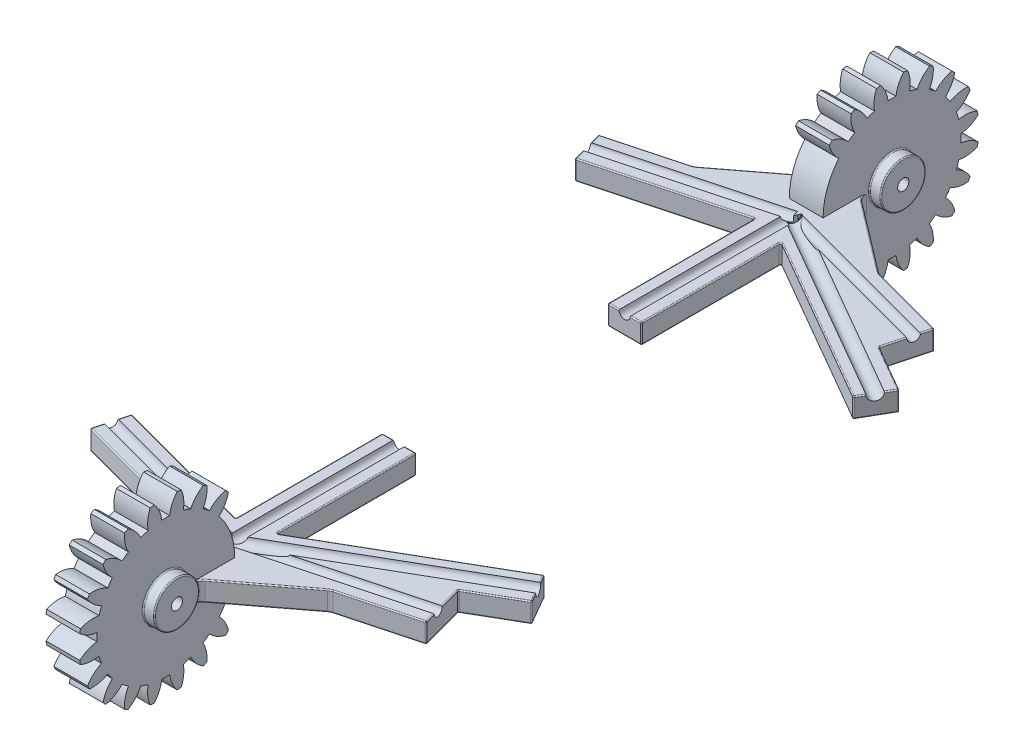
SolidWorks part; units mm, degrees
ref_plane "Plane1" through (0, 0, 0) normal (0, 0, 1) x (1, 0, 0)
ref_plane "Plane2" through (0, 0, 0) normal (0, 1, 0) x (1, 0, 0)
ref_plane "Plane3" through (0, 0, 0) normal (1, 0, 0) x (0, 0, -1)
other "Configuration Table"
sketch "HoldingSke" plane through (0, 0, 0) normal (0, 1, 0) x (1, 0, 0)
  line L0 (0, 0) -> (1.3424, -0.4886)
  line L1 (-15, 0) -> (100, 0) construction
  line L2 (0, 0) -> (-2.1039, 2.3779)
  line L3 (0, 0) -> (-11.863, 4.5341)
  line L4 (0, 0) -> (8.1152, 2.9537)
  line L5 (0, 0) -> (-46.8476, -17.4728)
  line L6 (0, 0) -> (-2.4869, -1.6779)
  line L7 (-2.1039, 2.3779) -> (8.6586, 51.2059)
  line L8 (-76.2, 54.61) -> (-76.1, 54.61)
  line L9 (-71.009, 38.7566) -> (-53.1078, 45.2721)
  line L10 (-76.2, 71.12) -> (104.1128, 71.12)
  line L11 (0, 0) -> (-3, 0)
  line L12 (-76.2, 101.6) -> (-76.173, 101.6)
  line L13 (24.9733, 27.94) -> (52.9518, 28.4284)
  line L14 (24.9733, 27.94) -> (24.9743, 27.94)
  line L15 (24.9733, 27.94) -> (100.4006, 29.5858)
  line L16 (-63.627, -0.7) -> (-12.827, -0.7)
  circle A0 centre (0, 0) radius 0.5
  circle A1 centre (0, 0) radius 6.124
  circle A2 centre (0, 0) radius 37.5
  circle A3 centre (0, 0) radius 0.5
  dimension "Num_teeth" = 20
  dimension "Pitch_radius" = 180.3128
  dimension "Width" = 3
  dimension "Thickness" = 3
sketch "BasProSke" plane through (0, 0, 0) normal (0, 1, 0) x (1, 0, 0)
  line L0 (-10, 0) -> (60, 0) construction
  line L1 (0, 0) -> (0, 7.7)
  line L2 (0, 0) -> (3, 0)
  line L3 (3, 0) -> (3, 7.7)
  line L4 (3, 7.7) -> (0, 7.7)
  dimension "Thickness" = 3
  dimension "Diameter" = 15.4
revolve "Base-Revolve" add sketch "BasProSke" angle 360 about L0
sketch "TooCutSke" plane through (0, 0, 0) normal (1, 0, 0) x (0, 0, -1)
  line L1 (0, 0) -> (0, 107) construction
  line L2 (0, 0) -> (-0.5964, 6.9745) construction
  line L3 (0, 0) -> (-2.1844, 13.792) construction
  line L4 (-0.5964, 6.9745) -> (-1.0922, 6.896) construction
  arc A0 (0.3505, 6.114) -> (-0.3505, 6.114) centre (0, 0) ccw
  arc A1 (1.0465, 7.6542) -> (-1.0465, 7.6542) centre (0, 0) ccw
  circle A2 centre (0, 0) radius 7 construction
  circle A3 centre (0, 0) radius 6.5778 construction
  arc A4 (-0.3505, 6.114) -> (-1.0465, 7.6542) centre (-3.1311, 5.7848) ccw
  arc A5 (1.0465, 7.6542) -> (0.3505, 6.114) centre (3.1311, 5.7848) ccw
extrude "ToothCut" cut sketch "TooCutSke" along normal through all
fillet "Breaks" [suppressed] radius 0.014 tangent propagation no
fillet "RootFillets" [suppressed] radius 0.176
pattern_circular "TeethCuts" count 20 every 18 about axis through (-10, 0, 0) along (1, 0, 0) of "ToothCut", "RootFillets", "Breaks"
sketch "HubNeaOneSke" plane through (0, 0, 0) normal (-1, 0, 0) x (0, 0, 1)
  circle A0 centre (0, 0) radius 6.124
  dimension "Diameter" = 12.248
extrude "HubNearOne" [suppressed] add sketch "HubNeaOneSke" along normal blind 47.0001
sketch "HubNeaBotSke" plane through (0, 0, 0) normal (-1, 0, 0) x (0, 0, 1)
  circle A0 centre (0, 0) radius 6.124
  dimension "Diameter" = 12.248
extrude "HubNearBoth" [suppressed] add sketch "HubNeaBotSke" along normal blind 23.5
ref_plane "FarPln" through (3, 0, 0) normal (1, 0, 0) x (0, 0, -1)
sketch "HubFarSke" plane through (3, 0, 0) normal (1, 0, 0) x (0, 0, -1)
  circle A0 centre (0, 0) radius 6.124
  dimension "Diameter" = 12.248
extrude "HubFar" [suppressed] add sketch "HubFarSke" along normal blind 23.5
sketch "BorSke" plane through (0, 0, 0) normal (1, 0, 0) x (0, 0, -1)
  circle A0 centre (0, 0) radius 0.5
  dimension "Diameter" = 1
extrude "Bore" cut sketch "BorSke" along normal mid plane 100.0001
sketch "KeySke" plane through (0, 0, 0) normal (1, 0, 0) x (0, 0, -1)
  line L0 (-0.05, 0) -> (-0.05, 0.6)
  line L1 (-0.05, 0.6) -> (0.05, 0.6)
  line L2 (0.05, 0.6) -> (0.05, 0)
  line L3 (0, 0) -> (0, 34) construction
  line L4 (-0.05, 0) -> (0.05, 0)
extrude "Keyway" [suppressed] cut sketch "KeySke" along normal mid plane 100.0001
pattern_circular "Keyway2" [suppressed] count 2 every 90 about axis through (-10, 0, 0) along (1, 0, 0)
sketch "草图1" plane through (3, 0, 0) normal (1, 0, 0) x (0, 0, -1)
  line L0 (4.9544, 3.5996) -> (6.3295, 4.5987)
  line L1 (4.9544, -3.5996) -> (6.3295, -4.5987)
  arc A0 (4.9544, 3.5996) -> (4.9544, -3.5996) centre (0, 0) cw
  arc A1 (5.1523, 3.3101) -> (4.7403, 3.8773) centre (0, 0) ccw construction
  arc A2 (4.7403, -3.8773) -> (5.1523, -3.3101) centre (0, 0) ccw construction
  arc A3 (6.3295, 4.5987) -> (6.3295, -4.5987) centre (-0.1229, 0) cw
extrude "切除-拉伸1" cut sketch "草图1" against normal through all
sketch "草图3" plane through (0, 0, 0) normal (0, 1, 0) x (1, 0, 0)
  line L0 (1.5, 6.0932) -> (1.5, 22.2442) construction
  line L2 (0, 6.0932) -> (3, 6.0932)
  line L3 (0, 6.124) -> (0, 4.7403) construction
  line L4 (3, 4.7403) -> (3, 6.124) construction
  line L5 (1.5, 7.2442) -> (-12.9889, 11.1265) construction
  line L6 (1.5, 7.2442) -> (18.8205, 17.2442) construction
  line L7 (1.5, 7.2442) -> (15.9889, 11.1265) construction
  line L8 (-12.6007, 12.5754) -> (-13.3771, 9.6776)
  line L9 (-13.3771, 9.6776) -> (0, 6.0932)
  line L10 (-12.6007, 12.5754) -> (0, 9.1991)
  line L11 (0, 9.1991) -> (0, 22.2442)
  line L12 (0, 22.2442) -> (3, 22.2442)
  line L13 (3, 22.2442) -> (3, 9.8423)
  line L14 (3, 9.8423) -> (18.0705, 18.5433)
  line L15 (18.0705, 18.5433) -> (19.5705, 15.9452)
  line L16 (19.5705, 15.9452) -> (15.4137, 13.5453)
  line L18 (15.4137, 13.5453) -> (16.4448, 9.6975)
  line L19 (16.4448, 9.6975) -> (3, 6.0949)
  line L20 (3, 6.0949) -> (3, 6.0932)
  dimension "D1" = 75
  dimension "D2" = 3
  dimension "D3" = 15
  dimension "D4" = 15
  dimension "D5" = 60
  dimension "D6" = 15
  dimension "D7" = 20
  dimension "D8" = 15
  dimension "D9" = 3
  dimension "D10" = 1.5
extrude "凸台-拉伸1" add sketch "草图3" against normal blind 1.75
sketch "草图4" plane through (0, 0, 0) normal (-1, 0, 0) x (0, 0, 1)
  line L0 (-6.0932, 0) -> (-6.0932, -1.75)
  line L1 (-6.0932, -1.75) -> (-5.6573, -2.3449)
  arc A0 (-6.0932, -0.6132) -> (-4.7403, -3.8773) centre (0, 0) ccw construction
  arc A1 (-5.6573, -2.3449) -> (-6.0932, 0) centre (127.3235, 23.5911) cw
extrude "凸台-拉伸3" add sketch "草图4" against normal blind 3
sketch "草图6" plane through (0, 0, 0) normal (0, 1, 0) x (1, 0, 0)
  line L0 (9.7224, 7.8962) -> (3, 2.7784)
  line L1 (3, 6.0949) -> (16.4448, 9.6975) construction
  line L2 (3, 2.2227) -> (3, 3.3342) construction
  line L3 (0, 2.7784) -> (-6.6886, 7.8854)
  line L4 (0, 3.3342) -> (0, 2.2227) construction
  line L5 (-13.3771, 9.6776) -> (0, 6.0932) construction
  line L6 (-6.6886, 7.8854) -> (0, 6.0932)
  line L7 (0, 6.0932) -> (0, 2.7784)
  line L8 (9.7224, 7.8962) -> (3, 6.0949)
  line L9 (3, 6.0949) -> (3, 2.7784)
extrude "凸台-拉伸5" add sketch "草图6" against normal blind 1.75
sketch "草图9" plane through (0, 0, -22.2442) normal (0, 0, -1) x (-1, 0, 0)
  line L0 (-3, 0) -> (0, 0) construction
  circle A0 centre (-1.5, 0) radius 0.5
sketch "草图10" plane through (-14.9004, 0, -3.9926) normal (-0.9659, 0, -0.2588) x (-0.2588, 0, 0.9659)
  line L0 (-8.8856, 0) -> (-5.8856, 0) construction
  circle A0 centre (-7.3856, 0) radius 0.5
fillet "圆角4" radius 0.1 18 edges at (17.4921, -1.75, -14.7452) (17.4921, 0, -14.7452) (-12.9889, 0, -11.1265) (-12.9889, -1.75, -11.1265) (-12.6007, -0.875, -12.5754) (-13.3771, -0.875, -9.6776) (1.5, -1.75, -22.2442) (3, -0.875, -22.2442) (0, -0.875, -22.2442) (1.5, 0, -22.2442) (18.8205, -1.75, -17.2442) (18.0705, -0.875, -18.5433) (18.8205, 0, -17.2442) (19.5705, -0.875, -15.9452) (15.9293, -1.75, -11.6214) (15.9293, 0, -11.6214) (15.4137, -0.875, -13.5453) (16.4448, -0.875, -9.6975)
fillet "圆角6" radius 1 1 edges at (9.7224, -0.875, -7.8962)
fillet "圆角7" radius 1 1 edges at (3, -0.875, -2.7784)
fillet "圆角8" radius 1 2 edges at (-6.6886, -0.875, -7.8854) (0, -0.875, -2.7784)
fillet "圆角9" radius 0.1 10 edges at (-0.1037, 0, -2.7272) (-0.1037, -1.75, -2.7272) (-3.4623, 0, -5.422) (-3.4623, -1.75, -5.422) (-13.3412, -0.0293, -9.6983) (-10.08, 0, -8.7942) (-6.6971, 0, -7.8681) (-13.3412, -1.7207, -9.6983) (-10.08, -1.75, -8.7942) (-6.6971, -1.75, -7.8681)
fillet "圆角10" radius 0.1 10 edges at (3.104, -1.75, -2.7269) (3.104, 0, -2.7269) (6.48, -1.75, -5.4278) (6.48, 0, -5.4278) (16.4089, -1.7207, -9.7182) (13.1304, -1.75, -8.8094) (9.7308, -1.75, -7.879) (16.4089, -0.0293, -9.7182) (13.1304, 0, -8.8094) (9.7308, 0, -7.879)
sketch "草图14" plane through (0, 0, 0) normal (-1, 0, 0) x (0, 0, 1)
  circle A0 centre (0, 0) radius 2
  circle A1 centre (0, 0) radius 0.5
extrude "凸台-拉伸7" add sketch "草图14" along normal blind 1
sketch "草图15" plane through (3, 0, 0) normal (1, 0, 0) x (0, 0, -1)
  circle A0 centre (0, 0) radius 2
  circle A1 centre (0, 0) radius 0.5
extrude "凸台-拉伸8" add sketch "草图15" along normal blind 1
fillet "圆角11" radius 0.1 1 edges at (4, 0, -2)
fillet "圆角12" radius 0.1 2 edges at (0, 0, -2) (-1, 0, 2)
fillet "圆角13" radius 0.1 1 edges at (3, 0, 2)
sketch "草图16" plane through (21.5823, 0, -12.4606) normal (0.866, 0, -0.5) x (-0.5, 0, -0.866)
  line L0 (4.1237, 0) -> (7.0237, 0) construction
  circle A0 centre (5.5737, 0) radius 0.6
  point P0 (5.5737, 0)
sketch "草图17" plane through (17.7675, 0, -4.7608) normal (0.9659, 0, -0.2588) x (-0.2588, 0, -0.9659)
  line L0 (5.2108, 0) -> (9.0176, 0) construction
  line L1 (5.1108, -1.65) -> (5.1108, -0.1) construction
  circle A0 centre (6.6108, 0) radius 0.5
  point P0 (6.6108, 0)
  dimension "D1" = 1.5
extrude "切除-拉伸2" cut sketch "草图9" against normal blind 15
extrude "切除-拉伸3" cut sketch "草图10" against normal blind 15
extrude "切除-拉伸4" cut sketch "草图16" against normal blind 20
extrude "切除-拉伸5" cut sketch "草图17" against normal blind 15
fillet "圆角14" radius 0.1 18 edges at (0.0293, -1.7207, -22.2149) (0.0293, -0.0293, -22.2149) (-12.5799, -0.0293, -12.5395) (-12.5799, -1.7207, -12.5395) (2.9707, -0.0293, -22.2149) (2.9707, -1.7207, -22.2149) (18.0598, -1.7207, -18.5032) (18.0598, -0.0293, -18.5032) (0, -1.75, -15.6716) (0, 0, -15.6716) (0, -0.875, -9.1991) (-6.252, 0, -10.8743) (-6.252, -1.75, -10.8743) (3, 0, -15.9933) (3, -1.75, -15.9933) (3, -0.875, -9.8423) (10.492, -1.75, -14.1678) (10.492, 0, -14.1678)
ref_plane "基准面1" through (0, 0, -32.2442) normal (0, 0, -1) x (-1, 0, 0)
mirror "镜向8" about plane through (0, 0, -32.2442) normal (0, 0, -1) of bodies 119
equation "' \"Module@HoldingSke\" = 6.35"
equation "' \"Num_teeth@HoldingSke\" = 12"
equation "' \"Ap@HoldingSke\" =  20"
equation "' \"Ap@HoldingSke\" = 20"
equation "' \"Width@HoldingSke\" = 0.5 * 25.4"
equation "' \"Hub_dia@HoldingSke\"= 1 * 25.4"
equation "' \"Hub_dia@HoldingSke\" = 1 * 25.4"
equation "' \"Overall_len@HoldingSke\" = 1.0 * 25.4"
equation "' \"Bore@HoldingSke\" = 0.75 * 25.4"
equation "' \"T_dim@HoldingSke\" = 0.1 * 25.4"
equation "' \"Width@KeySke\" = 0.25 * 25.4"
equation "' \"Show_teeth@HoldingSke\" = 13"
equation "' \"Backlash@HoldingSke\" = 0.009 * 25.4"
equation "' \"Addendum_fac@HoldingSke\" = 1.0"
equation "' \"Dedendum_fac@HoldingSke\" = 1.25"
equation "' \"Dedendum_add@HoldingSke\" = 0.00005 * 25.4"
equation "' \"Clearance_fac@HoldingSke\" = 0.25"
equation "\"Pitch@HoldingSke\" = 1 / \"Module@HoldingSke\""
equation "\"Overcut_dia@TooCutSke\" = (\"Num_teeth@HoldingSke\" + 2 * \"Addendum_fac@HoldingSke\") / \"Pitch@HoldingSke\" + 0.002 * 25.4"
equation "\"Pitch_dia@TooCutSke\" = \"Num_teeth@HoldingSke\" / \"Pitch@HoldingSke\""
equation "\"Base_dia@TooCutSke\" = \"Num_teeth@HoldingSke\" / \"Pitch@HoldingSke\" * cos((\"Ap@HoldingSke\"  * 3.14159265 / 180))"
equation "\"Root_dia@TooCutSke\" = (\"Num_teeth@HoldingSke\" + 2) / \"Pitch@HoldingSke\" - 2 * (\"Addendum_fac@HoldingSke\" + \"Dedendum_fac@HoldingSke\") / \"Pitch@HoldingSke\" - \"Dedendum_add@HoldingSke\" * 2"
equation "\"Half_ang@TooCutSke\" = 180 / \"Num_teeth@HoldingSke\""
equation "\"Half_CT@TooCutSke\" = \"Num_teeth@HoldingSke\" / \"Pitch@HoldingSke\" * sin((3.14159265 / 2 / \"Num_teeth@HoldingSke\")) / 2 - 7 * \"Backlash@HoldingSke\" / 4"
equation "\"Flank_rad@TooCutSke\" = \"Num_teeth@HoldingSke\" / \"Pitch@HoldingSke\" / 5"
equation "\"Radius@RootFillets\" = \"Clearance_fac@HoldingSke\" / \"Pitch@HoldingSke\" + \"Dedendum_add@HoldingSke\""
equation "\"Break_rad@Breaks\" = 0.02 / \"Pitch@HoldingSke\""
equation "\"Thickness@HoldingSke\" = \"Width@HoldingSke\""
equation "\"OAL@HoldingSke\" = \"Thickness@HoldingSke\""
equation "\"MHD@HoldingSke\" = (\"Num_teeth@HoldingSke\" + 2) / \"Pitch@HoldingSke\" - 2 * (\"Addendum_fac@HoldingSke\" + \"Dedendum_fac@HoldingSke\")  / \"Pitch@HoldingSke\" - \"Dedendum_add@HoldingSke\" * 2"
equation "\"MBD@HoldingSke\" = (\"Num_teeth@HoldingSke\" + 2) / \"Pitch@HoldingSke\" - 2 * (\"Addendum_fac@HoldingSke\" + \"Dedendum_fac@HoldingSke\")  / \"Pitch@HoldingSke\" - \"Dedendum_add@HoldingSke\" * 2 - 0.002 * 25.4"
equation "\"MHD@HoldingSke\" = ((sgn( \"MHD@HoldingSke\" - \"Hub_dia@HoldingSke\" )-1)*( \"MHD@HoldingSke\" - \"Hub_dia@HoldingSke\" ))/-2+ \"Hub_dia@HoldingSke\""
equation "\"MBD@HoldingSke\" = ((sgn( \"MBD@HoldingSke\" - \"Bore@HoldingSke\" )-1)*( \"MBD@HoldingSke\" - \"Bore@HoldingSke\" ))/-2+ \"Bore@HoldingSke\""
equation "\"OAL@HoldingSke\" = ((sgn( \"OAL@HoldingSke\" - \"Overall_len@HoldingSke\" )+1)*( \"OAL@HoldingSke\" - \"Overall_len@HoldingSke\" ))/2 + \"Overall_len@HoldingSke\" + 0.000002 * 25.4"
equation "\"Num_teeth@TeethCuts\" = int( \"Show_teeth@HoldingSke\" ) + 1"
equation "\"Num_teeth@TeethCuts\" = ((sgn( \"Num_teeth@TeethCuts\" - \"Num_teeth@HoldingSke\" )-1)*( \"Num_teeth@TeethCuts\" - \"Num_teeth@HoldingSke\" ))/-2+ \"Num_teeth@HoldingSke\""
equation "\"Num_teeth@TeethCuts\" = ((sgn( \"Num_teeth@TeethCuts\" - 2.0)+1)*( \"Num_teeth@TeethCuts\" - 2.0))/2 +2.0"
equation "\"Angle@TeethCuts\" = 360.0 / \"Num_teeth@HoldingSke\""
equation "\"Diameter@BasProSke\" = (\"Num_teeth@HoldingSke\" + 2 * \"Addendum_fac@HoldingSke\") / \"Pitch@HoldingSke\""
equation "\"Thickness@BasProSke\"  = \"Thickness@HoldingSke\""
equation "' \"Fillet_rad@BasProSke\" =  \"Thickness@HoldingSke\" * 0.05"
equation "' \"Fillet_rad@BasProSke\" = \"Thickness@HoldingSke\" * 0.05"
equation "\"MHD@HoldingSke\" = ((sgn( \"MHD@HoldingSke\" - \"Root_dia@TooCutSke\" )-1)*( \"MHD@HoldingSke\" - \"Root_dia@TooCutSke\" ))/-2+ \"Root_dia@TooCutSke\""
equation "\"Diameter@HubNeaOneSke\" = \"MHD@HoldingSke\""
equation "\"Length@HubNearOne\" = \"OAL@HoldingSke\" - \"Thickness@BasProSke\""
equation "\"Diameter@HubNeaBotSke\" = \"MHD@HoldingSke\""
equation "\"Length@HubNearBoth\" = ( \"OAL@HoldingSke\" - \"Thickness@BasProSke\" ) / 2.0"
equation "\"Thickness@FarPln\" = \"Thickness@BasProSke\""
equation "\"Diameter@HubFarSke\" = \"MHD@HoldingSke\""
equation "\"Length@HubFar\" = ( \"OAL@HoldingSke\" - \"Thickness@BasProSke\" ) / 2.0"
equation "\"Diameter@BorSke\" = \"MBD@HoldingSke\""
equation "\"D1@Bore\" = \"OAL@HoldingSke\" * 2.0"
equation "\"D1@Keyway\" = \"OAL@HoldingSke\" * 2.0"
equation "\"Offset@KeySke\" = \"T_dim@HoldingSke\" + \"MBD@HoldingSke\" / 2.0"
